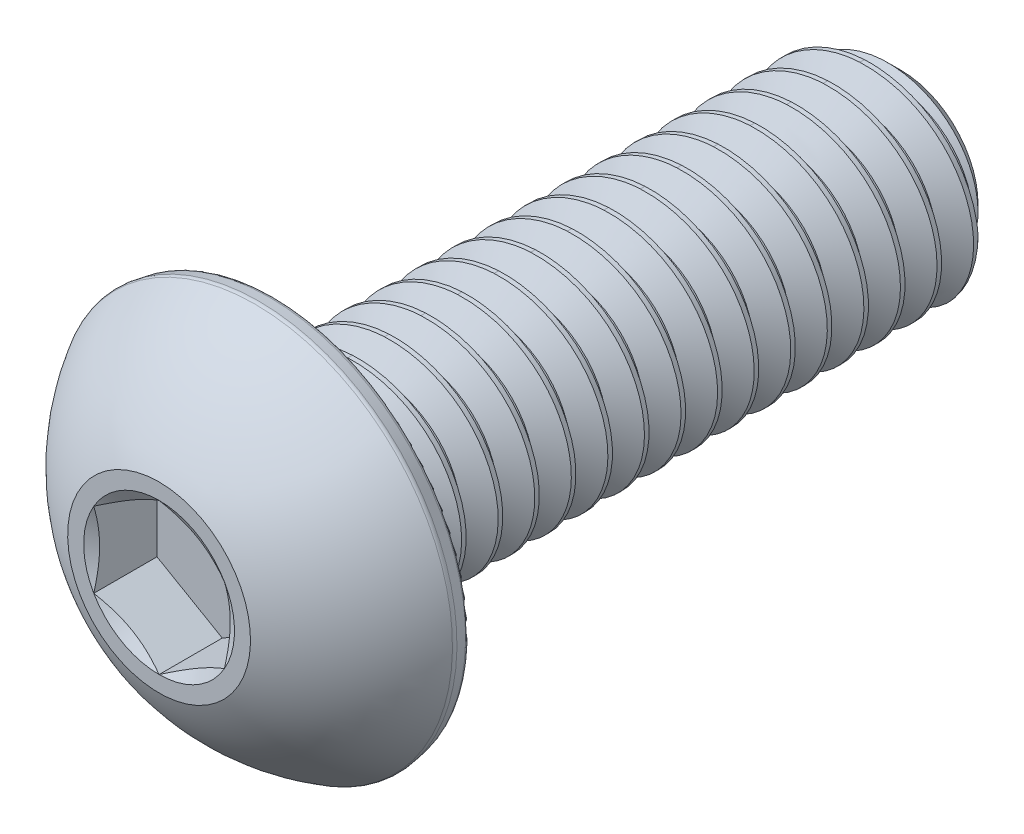
SolidWorks part; units mm, degrees
ref_plane "Front Plane" through (0, 0, 0) normal (0, 0, 1) x (1, 0, 0)
ref_plane "Top Plane" through (0, 0, 0) normal (0, 1, 0) x (1, 0, 0)
ref_plane "Right Plane" through (0, 0, 0) normal (1, 0, 0) x (0, 0, -1)
sketch "Sketch1" plane through (0, 0, 0) normal (1, 0, 0) x (0, 0, -1)
  line L0 (0, 0) -> (12, 0) construction
  line L1 (12, 2) -> (12, -2) construction
  line L2 (0, 0) -> (-2.2, 0) construction
  line L3 (0, 3.8) -> (0, -3.8) construction
  line L4 (-2.2, 1.25) -> (-2.2, -1.25) construction
  line L5 (11.9563, 2.0758) -> (12.6563, 2.0758) construction
  line L6 (12.6563, 2.0758) -> (12.3063, 1.4696) construction
  line L7 (12.3063, 1.4696) -> (11.9563, 2.0758) construction
  line L8 (11.9781, 2.0379) -> (12.6344, 2.0379) construction
  line L9 (12, 2) -> (12.6125, 2) construction
  line L10 (12.2625, 1.5453) -> (12.35, 1.5453) construction
  line L11 (12.3063, 1.5453) -> (12.3063, 1.4696) construction
  line L12 (12.3063, 2) -> (12.3063, 2.0758) construction
  point P5 (12, 0)
  point P10 (-2.2, 0)
  point P13 (0, 0)
  point P18 (10.25, -2)
  point P25 (12.3063, 2.0379)
  dimension "Thread Size" = 4
  dimension "Length" = 12
  dimension "Head Diameter" = 7.6
  dimension "Drive Size" = 2.5
  dimension "Head Height" = 2.2
  dimension "D1" = 60
  dimension "Thread Pitch" = 0.7
  dimension "D2" = 0.0875
  dimension "D3" = 1.75
sketch "Sketch2" plane through (0, 0, 0) normal (1, 0, 0) x (0, 0, -1)
  line L0 (12, 0) -> (-2.2, 0)
  line L1 (-2.2, 0) -> (-2.2, 1.75)
  line L2 (-2.2, 0) -> (-2.2, 3.8) construction
  line L3 (-2.2, 3.8) -> (0, 3.8) construction
  line L4 (0, 3.7418) -> (-0.33, 3.8)
  line L5 (0, 3.8) -> (0, -3.8) construction
  line L6 (0, 3.7418) -> (0, 2)
  line L7 (0, 2) -> (11.475, 2)
  line L8 (11.475, 2) -> (12, 1.475)
  line L9 (12, 2) -> (12, -2) construction
  line L10 (12, 1.475) -> (12, 0)
  line L11 (-2.2, 0) -> (-2.2, -1.75) construction
  arc A0 (-0.33, 3.8) -> (-2.2, 1.75) centre (1.7771, 0) ccw
  dimension "D1" = 45
  dimension "D2" = 0.525
  dimension "D3" = 10
  dimension "D4" = 0.33
  dimension "D5" = 3.5
revolve "Revolve1" add sketch "Sketch2" angle 360 about L0
sketch "Sketch3" plane through (0, 0, 2.2) normal (0, 0, 1) x (1, 0, 0)
  line L1 (0, 1.4434) -> (-1.25, 0.7217)
  line L2 (-1.25, 0.7217) -> (-1.25, -0.7217)
  line L3 (-1.25, -0.7217) -> (0, -1.4434)
  line L4 (0, -1.4434) -> (1.25, -0.7217)
  line L5 (1.25, -0.7217) -> (1.25, 0.7217)
  line L6 (1.25, 0.7217) -> (0, 1.4434)
  circle A0 centre (0, 0) radius 1.25 construction
extrude "Cut-Extrude1" cut sketch "Sketch3" against normal blind 1.21
sketch "Sketch4" plane through (0, 0, 2.2) normal (0, 0, 1) x (1, 0, 0)
  circle A0 centre (0, 0) radius 1.4434
extrude "Cut-Extrude2" cut sketch "Sketch4" against normal blind 1.21 draft 60
fillet "Fillet1" radius 0.11 2 edges at (0, 3.8, 0.33) (0, 3.7418, 0)
sketch "Sketch8" plane through (0, 0, 0) normal (0, 0, 1) x (1, 0, 0)
  circle A0 centre (0, 0) radius 3.8 construction
  circle A1 centre (0, 0) radius 1.25 construction
ref_plane "Plane1" through (0, 0, -0.315) normal (0, 0, 1) x (1, 0, 0)
split "Split1" trim tools "Plane1" bodies to split 106 resulting bodies 107 108
sketch "Sketch5" plane through (0, 0, 0) normal (1, 0, 0) x (0, 0, -1)
  line L0 (11.9781, 2.0379) -> (12.6344, 2.0379)
  line L1 (12.6344, 2.0379) -> (12.35, 1.5453)
  line L2 (12.35, 1.5453) -> (12.2625, 1.5453)
  line L3 (12.2625, 1.5453) -> (11.9781, 2.0379)
sketch "Sketch6" plane through (0, 0, -12) normal (0, 0, -1) x (-1, 0, 0)
  circle A0 centre (0, 0) radius 2
curve "Helix/Spiral1" pitch 0.7 height 12.7 radius 2 centre (0, 0, -12) axis (0, 0, 1) start towards (0, 1, 0)
sweep "Cut-Sweep1" cut profiles "Sketch5" path "Helix/Spiral1" align with end faces yes
combine bodies "Combine1" operation type add bodies to combine 109 107
sketch "Sketch7" plane through (0, 0, -0.315) normal (0, 0, 1) x (1, 0, 0)
  circle A0 centre (0, 0) radius 2
extrude "Boss-Extrude1" add sketch "Sketch7" against normal blind 1.75 draft 45
fillet "Fillet2" radius 0.11 1 edges at (0, 2, 0)
equation "\"D2@Sketch1\"=\"Thread Pitch@Sketch1\"/8"
equation "\"D2@Sketch2\"=\"Thread Pitch@Sketch1\"*.75"
equation "\"D4@Sketch2\"=\"Head Height@Sketch1\"*.15"
equation "\"D5@Sketch2\"=\"Drive Size@Sketch1\"*1.4"
equation "\"D1@Cut-Extrude1\"=\"Head Height@Sketch1\"*.55"
equation "\"D1@Cut-Extrude2\"=\"D1@Cut-Extrude1\""
equation "\"D1@Fillet1\"=\"Head Height@Sketch1\"*.05"
equation "\"D4@Helix/Spiral1\"=\"Thread Pitch@Sketch1\""
equation "\"D3@Helix/Spiral1\"=\"Length@Sketch1\"+\"Thread Pitch@Sketch1\""
equation "\"D3@Sketch1\"=\"Thread Pitch@Sketch1\"*2.5"
equation "\"D1@Fillet2\"=\"D1@Fillet1\""
equation "\"D1@Plane1\"=\"Thread Pitch@Sketch1\"*.45"
equation "\"D1@Boss-Extrude1\"=\"Thread Pitch@Sketch1\"*2.5"
